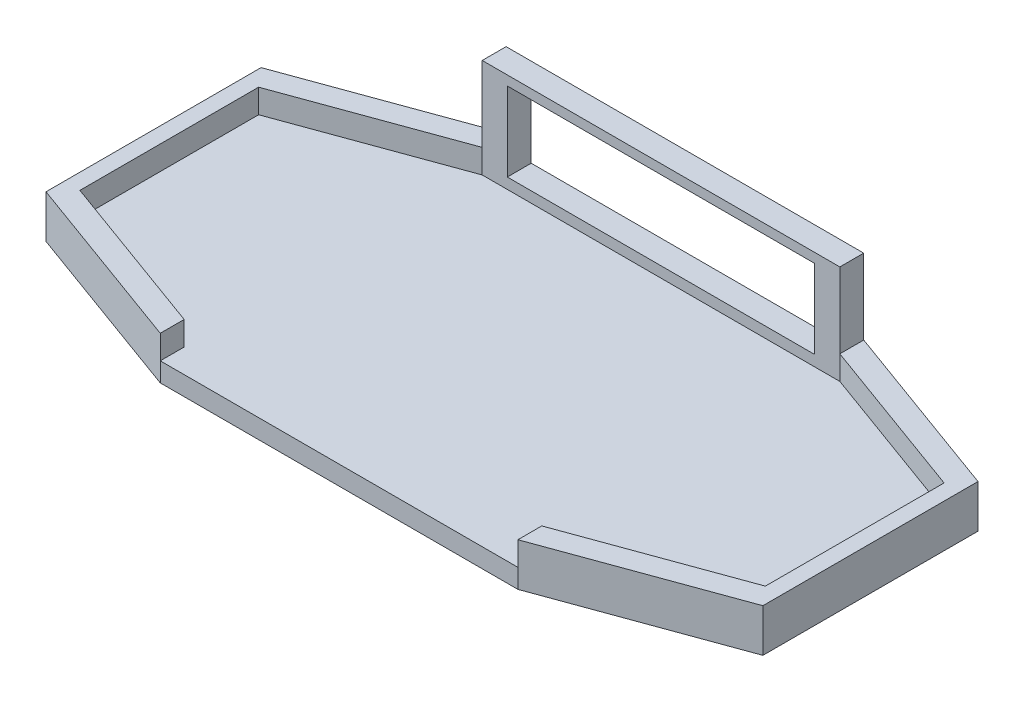
SolidWorks part; units mm, degrees
material "ABS"
ref_plane "Front Plane" through (0, 0, 0) normal (0, 0, 1) x (1, 0, 0)
ref_plane "Top Plane" through (0, 0, 0) normal (0, 1, 0) x (1, 0, 0)
ref_plane "Right Plane" through (0, 0, 0) normal (1, 0, 0) x (0, 0, -1)
sketch "Sketch1" plane through (0, 0, 0) normal (0, 1, 0) x (1, 0, 0)
  line L0 (-150, 0) -> (150, 0) construction
  line L1 (-150, 45) -> (-150, -45)
  line L2 (140.0883, -41.1583) -> (79.948, -63.0476) construction
  line L3 (-140.0883, 41.1583) -> (-142.4825, 47.7362) construction
  line L4 (-140.0883, 41.1583) -> (-79.948, 63.0476) construction
  line L5 (-150, 45) -> (-74.8246, 72.3616)
  line L6 (-79.948, 63.0476) -> (-82.3421, 69.6255) construction
  line L7 (-143, 32) -> (-143, -32) construction
  line L8 (-140.0883, -41.1583) -> (-142.4825, -47.7362) construction
  line L9 (-79.948, -63.0476) -> (-82.3421, -69.6255) construction
  line L10 (-140.0883, -41.1583) -> (-79.948, -63.0476) construction
  line L11 (-150, -45) -> (-74.8246, -72.3616)
  line L12 (0, 74.8501) -> (0, -82.9126) construction
  line L13 (79.948, -63.0476) -> (82.3421, -69.6255) construction
  line L14 (140.0883, -41.1583) -> (142.4825, -47.7362) construction
  line L15 (143, 32) -> (143, -32) construction
  line L16 (79.948, 63.0476) -> (82.3421, 69.6255) construction
  line L17 (140.0883, 41.1583) -> (79.948, 63.0476) construction
  line L18 (140.0883, 41.1583) -> (142.4825, 47.7362) construction
  line L19 (150, -45) -> (74.8246, -72.3616)
  line L20 (150, 45) -> (74.8246, 72.3616)
  line L21 (150, 45) -> (150, -45)
  line L22 (-74.8246, 72.3616) -> (74.8246, 72.3616)
  line L23 (-74.8246, -72.3616) -> (74.8246, -72.3616)
  point P0 (0, 0)
  point P3 (-150, 0)
  point P10 (-143, 0)
  point P13 (0, 0)
  point P37 (143, 0)
  dimension "D1" = 7
  dimension "D2" = 90
  dimension "D3" = 64
  dimension "D4" = 300
  dimension "D5" = 7
  dimension "D6" = 8
  dimension "D7" = 80
  dimension "D8" = 110
extrude "Boss-Extrude1" add sketch "Sketch1" along normal blind 8
sketch "Sketch2" plane through (0, 8, 0) normal (0, 1, 0) x (1, 0, 0)
  line L0 (0, 72.3616) -> (0, -72.3616) construction
  line L1 (74.8246, 72.3616) -> (-74.8246, 72.3616) construction
  line L2 (-74.8246, -72.3616) -> (74.8246, -72.3616) construction
  line L3 (-74.8246, -72.3616) -> (-74.8246, -62.3616) construction
  line L4 (-74.8246, -62.3616) -> (-64.3246, -62.3616) construction
  line L5 (-64.3246, -62.3616) -> (-64.3246, -72.3616) construction
  line L6 (-64.3246, -72.3616) -> (-74.8246, -72.3616) construction
  line L7 (64.3246, -72.3616) -> (74.8246, -72.3616) construction
  line L8 (64.3246, -62.3616) -> (64.3246, -72.3616) construction
  line L9 (74.8246, -62.3616) -> (64.3246, -62.3616) construction
  line L10 (74.8246, -72.3616) -> (74.8246, -62.3616) construction
  line L11 (-150, 0) -> (150, 0) construction
  line L12 (-150, 45) -> (-150, -45) construction
  line L13 (150, -45) -> (150, 45) construction
  line L14 (74.8246, 72.3616) -> (74.8246, 62.3616)
  line L15 (74.8246, 62.3616) -> (64.3246, 62.3616)
  line L16 (64.3246, 62.3616) -> (64.3246, 72.3616)
  line L17 (64.3246, 72.3616) -> (74.8246, 72.3616)
  line L18 (-64.3246, 72.3616) -> (-74.8246, 72.3616)
  line L19 (-64.3246, 62.3616) -> (-64.3246, 72.3616)
  line L20 (-74.8246, 62.3616) -> (-64.3246, 62.3616)
  line L21 (-74.8246, 72.3616) -> (-74.8246, 62.3616)
  dimension "D1" = 10.5
  dimension "D2" = 10
extrude "Boss-Extrude2" add sketch "Sketch2" along normal blind 37.5
sketch "Sketch4" plane through (0, 8, 0) normal (0, 1, 0) x (1, 0, 0)
  line L1 (-64.3246, 72.3616) -> (64.3246, 72.3616)
  line L2 (-64.3246, 72.3616) -> (-64.3246, 62.3616)
  line L3 (-64.3246, 62.3616) -> (64.3246, 62.3616)
  line L4 (64.3246, 72.3616) -> (64.3246, 62.3616)
extrude "Boss-Extrude4" add sketch "Sketch4" along normal blind 4.5
sketch "Sketch5" plane through (0, 8, 0) normal (0, 1, 0) x (1, 0, 0)
  line L0 (-74.8246, 62.3616) -> (-87.0406, 57.9153)
  line L1 (-74.8246, 72.3616) -> (-150, 45) construction
  line L2 (-74.8246, 72.3616) -> (-74.8246, 62.3616)
  line L3 (-74.8246, 72.3616) -> (-150, 45)
  line L4 (-87.0406, 57.9153) -> (-140.6031, 38.4202)
  line L5 (-150, 45) -> (-140.6031, 38.4202) construction
  line L6 (-74.8246, -72.3616) -> (-74.8246, -62.3616)
  line L7 (-140.6031, 38.4202) -> (-143.4222, 37.3941)
  line L8 (-150, 45) -> (-143.4222, 37.3941) construction
  line L9 (-150, 0) -> (-74.8246, 0) construction
  line L10 (-150, 45) -> (-150, -45) construction
  line L11 (-79.6003, 0) -> (86.9407, 0) construction
  line L12 (-121.6693, 0) -> (-119.4693, 0) construction
  line L13 (-74.8246, -62.3616) -> (-87.0406, -57.9153)
  line L14 (-140.6031, -38.4202) -> (-143.4222, -37.3941)
  line L15 (-87.0406, -57.9153) -> (-140.6031, -38.4202)
  line L16 (-150, -45) -> (-143.4222, -37.3941) construction
  line L17 (-74.8246, -72.3616) -> (-150, -45)
  line L18 (-143.4222, 37.3941) -> (-143.4222, -37.3941)
  line L19 (-150, 45) -> (-150, -45)
  line L20 (0, 72.1209) -> (0, -72.3616) construction
  line L21 (-74.8246, -72.3616) -> (74.8246, -72.3616) construction
  line L22 (150, -45) -> (143.4222, -37.3941) construction
  line L23 (150, 0) -> (74.8246, 0) construction
  line L24 (150, 45) -> (143.4222, 37.3941) construction
  line L25 (150, 45) -> (140.6031, 38.4202) construction
  line L26 (150, 45) -> (150, -45)
  line L27 (143.4222, 37.3941) -> (143.4222, -37.3941)
  line L28 (74.8246, -72.3616) -> (150, -45)
  line L29 (87.0406, -57.9153) -> (140.6031, -38.4202)
  line L30 (140.6031, -38.4202) -> (143.4222, -37.3941)
  line L31 (74.8246, -62.3616) -> (87.0406, -57.9153)
  line L32 (140.6031, 38.4202) -> (143.4222, 37.3941)
  line L33 (74.8246, -72.3616) -> (74.8246, -62.3616)
  line L34 (87.0406, 57.9153) -> (140.6031, 38.4202)
  line L35 (74.8246, 72.3616) -> (150, 45)
  line L36 (74.8246, 72.3616) -> (74.8246, 62.3616)
  line L37 (74.8246, 62.3616) -> (87.0406, 57.9153)
  dimension "D1" = 13
  dimension "D2" = 55
  dimension "D3" = 3
extrude "Boss-Extrude5" add sketch "Sketch5" along normal blind 10
sketch "Sketch6" plane through (0, 45.5, 0) normal (0, 1, 0) x (1, 0, 0)
  line L1 (74.8246, 72.3616) -> (-74.8246, 72.3616)
  line L2 (74.8246, 72.3616) -> (74.8246, 62.3616)
  line L3 (74.8246, 62.3616) -> (-74.8246, 62.3616)
  line L4 (-74.8246, 72.3616) -> (-74.8246, 62.3616)
extrude "Boss-Extrude6" add sketch "Sketch6" along normal blind 4
